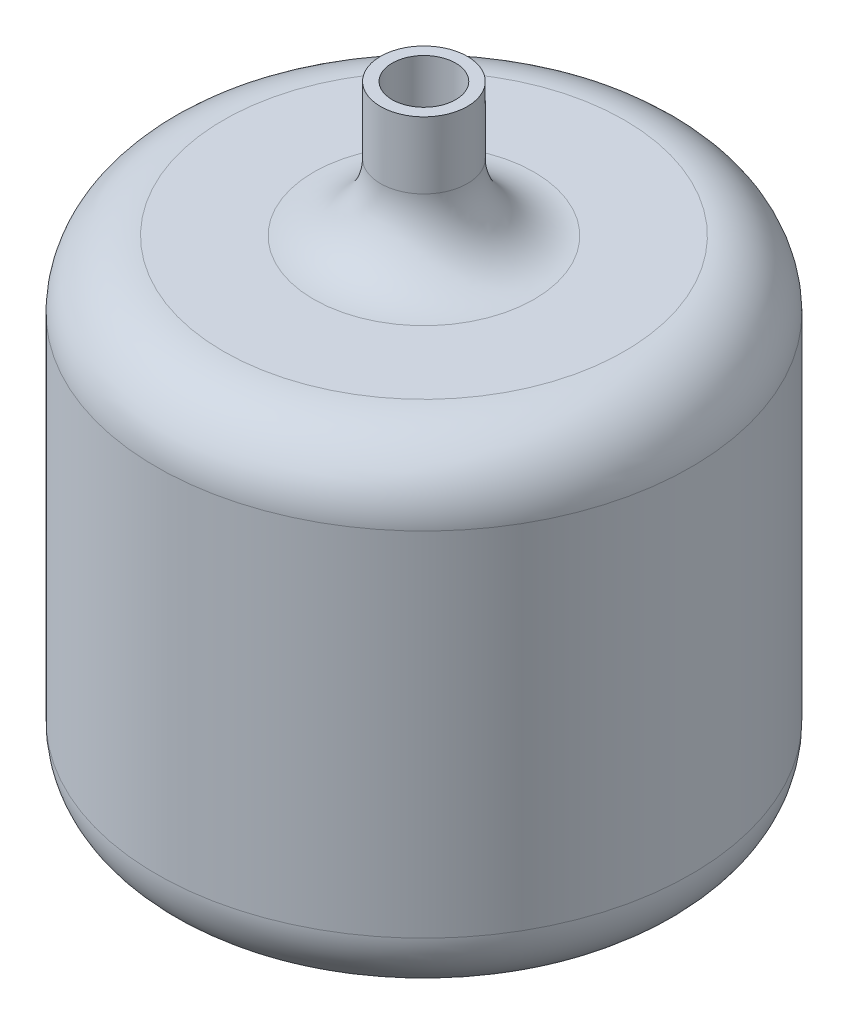
SolidWorks part; units mm, degrees
ref_plane "Plan de face" through (0, 0, 0) normal (1, 0, 0) x (0, 1, 0)
ref_plane "Plan de dessus" through (0, 0, 0) normal (0, 0, 1) x (0, 1, 0)
ref_plane "Plan de droite" through (0, 0, 0) normal (0, 1, 0) x (-1, 0, 0)
sketch "Esquisse1" plane through (0, 0, 0) normal (0, 0, 1) x (0, 1, 0)
  line L0 (0, 0) -> (64.4456, 0) construction
  line L1 (-31.0702, 40) -> (31.9298, 40)
  line L2 (-31.0702, 40) -> (-31.0702, 32.5)
  line L3 (-31.0702, 32.5) -> (31.9298, 32.5)
  line L4 (31.9298, 40) -> (31.9298, 32.5)
  line L5 (31.9298, 40) -> (41.9298, 40)
  line L6 (31.9298, 40) -> (31.9298, -40)
  line L7 (31.9298, -40) -> (41.9298, -40)
  line L8 (41.9298, 40) -> (41.9298, -40)
  line L9 (31.9298, -40) -> (-30.5263, -40)
  line L10 (31.9298, -40) -> (31.9298, -32.5)
  line L11 (31.9298, -32.5) -> (-30.5263, -32.5)
  line L12 (-30.5263, -40) -> (-30.5263, -32.5)
  dimension "D1" = 7.5
  dimension "D2" = 7.5
  dimension "D3" = 10
  dimension "D4" = 80
  dimension "D5" = 32.5
  dimension "D6" = 63
revolve "Révolution1" add sketch "Esquisse1" angle 360 about L0 region at (20, 36.9298, 0) region at (36.25, 0.7018, 0)
sketch "Esquisse2" plane through (0, 0, 0) normal (1, 0, 0) x (0, 1, 0)
  line L0 (-30.5263, 40) -> (-30.5263, -40) construction
  circle A0 centre (-20.5263, 0) radius 5.5
  circle A1 centre (-5.5263, 0) radius 5.5
  circle A2 centre (9.4737, 0) radius 5.5
  circle A3 centre (24.4737, 0) radius 5.5
  dimension "D1" = 11
  dimension "D3" = 11
  dimension "D5" = 11
  dimension "D7" = 11
  dimension "D2" = 10
  dimension "D4" = 15
  dimension "D6" = 15
  dimension "D8" = 15
extrude "Enlèv. mat.-Extru.1" cut sketch "Esquisse2" against normal blind 33
pattern_circular "Répétition circulaire1" count 15 every 24 about axis through (0, -30.5263, 0) along (0, -1, 0) of "Enlèv. mat.-Extru.1"
fillet "Congé1" radius 10 1 edges at (0, 41.9298, -40)
fillet "Congé2" radius 10 1 edges at (0, -30.5263, -40)
sketch "Esquisse3" plane through (0, 41.9298, 0) normal (0, 1, 0) x (-1, 0, 0)
  circle A0 centre (0, 0) radius 6.5
  circle A1 centre (0, 0) radius 4.75
  dimension "D1" = 13
  dimension "D2" = 9.5
extrude "Boss.-Extru.1" add sketch "Esquisse3" along normal blind 20
fillet "Congé3" radius 10 1 edges at (0, 41.9298, -6.5)
